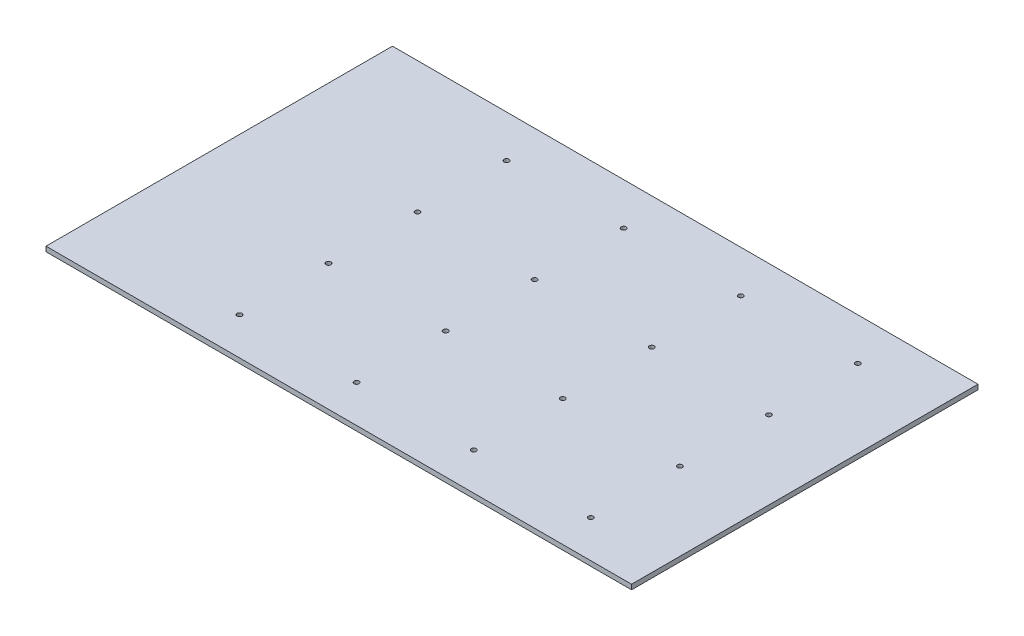
SolidWorks part; units mm, degrees
material "Acrylic (Medium-high impact)"
ref_plane "Front Plane" through (0, 0, 0) normal (0, 0, 1) x (1, 0, 0)
ref_plane "Top Plane" through (0, 0, 0) normal (0, 1, 0) x (1, 0, 0)
ref_plane "Right Plane" through (0, 0, 0) normal (1, 0, 0) x (0, 0, -1)
sketch "Sketch1" plane through (0, 0, 0) normal (0, 1, 0) x (1, 0, 0)
  line L1 (0, 0) -> (762, 0)
  line L2 (0, 0) -> (0, 450.85)
  line L3 (0, 450.85) -> (762, 450.85)
  line L4 (762, 0) -> (762, 450.85)
  dimension "D1" = 450.85
  dimension "D2" = 762
extrude "Boss-Extrude1" add sketch "Sketch1" along normal blind 6.35
sketch "Sketch2" plane through (0, 6.35, 0) normal (0, 1, 0) x (1, 0, 0)
  line L0 (0, 396.0876) -> (762, 396.0876) construction
  line L1 (0, 450.85) -> (0, 0) construction
  line L2 (762, 0) -> (762, 450.85) construction
  line L3 (762, 450.85) -> (0, 450.85) construction
  line L4 (0, 280.1874) -> (762, 280.1874) construction
  line L5 (0, 164.2872) -> (762, 164.2872) construction
  line L6 (0, 48.387) -> (762, 48.387) construction
  circle A0 centre (203.2, 396.0876) radius 3.175
  circle A1 centre (355.6, 396.0876) radius 3.175
  circle A2 centre (508, 396.0876) radius 3.175
  circle A3 centre (660.4, 396.0876) radius 3.175
  circle A4 centre (203.2, 280.2636) radius 3.175
  circle A5 centre (355.6, 280.2636) radius 3.175
  circle A6 centre (508, 280.2636) radius 3.175
  circle A7 centre (660.4, 280.2636) radius 3.175
  circle A8 centre (203.2, 164.4396) radius 3.175
  circle A9 centre (355.6, 164.4396) radius 3.175
  circle A10 centre (508, 164.4396) radius 3.175
  circle A11 centre (660.4, 164.4396) radius 3.175
  circle A12 centre (203.2, 48.6156) radius 3.175
  circle A13 centre (355.6, 48.6156) radius 3.175
  circle A14 centre (508, 48.6156) radius 3.175
  circle A15 centre (660.4, 48.6156) radius 3.175
  dimension "D4" = 6.35
  dimension "D1" = 54.7624
  dimension "D3" = 115.9002
  dimension "D5" = 203.2
  dimension "D7" = 152.4
  dimension "D9" = 115.824
  dimension "D2" = 4
  dimension "D6" = 4
  dimension "D8" = 4
extrude "Cut-Extrude1" cut sketch "Sketch2" against normal blind 6.35
